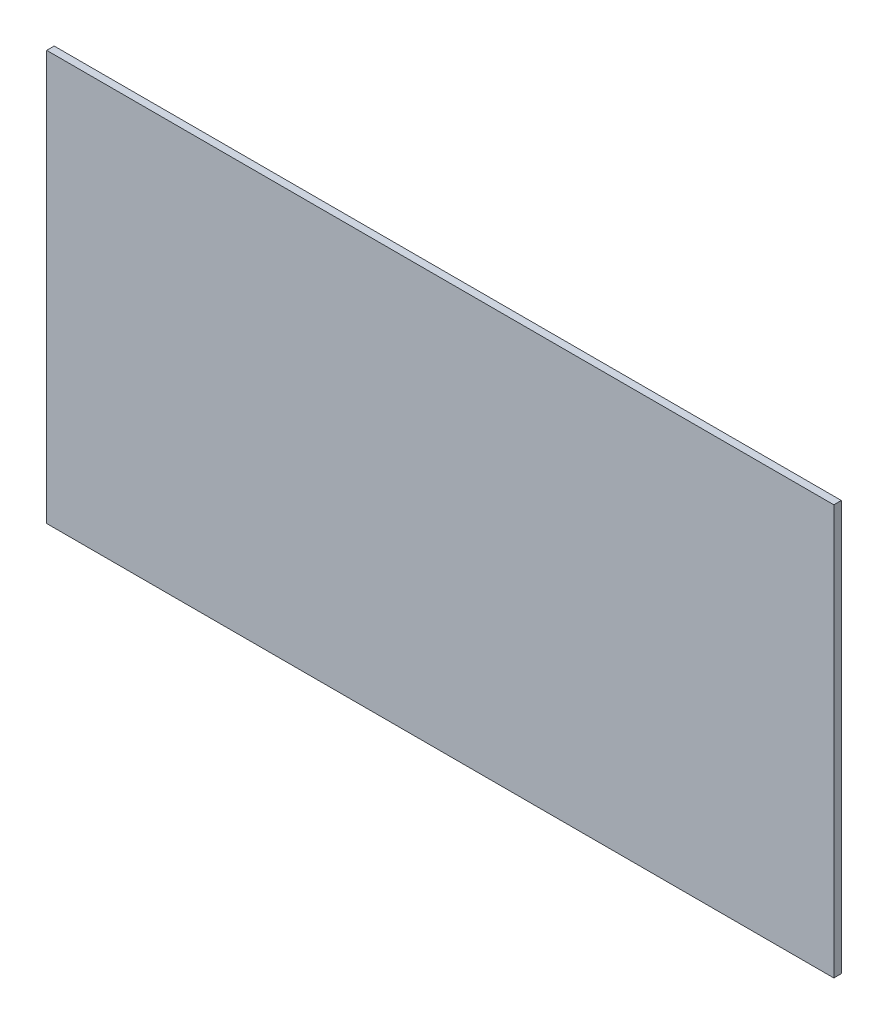
SolidWorks part; units mm, degrees
ref_plane "Ön Düzlem" through (0, 0, 0) normal (0, 0, 1) x (1, 0, 0)
ref_plane "Üst Düzlem" through (0, 0, 0) normal (0, 1, 0) x (1, 0, 0)
ref_plane "Sağ Düzlem" through (0, 0, 0) normal (1, 0, 0) x (0, 0, -1)
sketch "Çizim1" plane through (0, 0, 0) normal (0, 0, 1) x (1, 0, 0)
  line L1 (0, 0) -> (630, 0)
  line L2 (0, 0) -> (0, -328)
  line L3 (0, -328) -> (630, -328)
  line L4 (630, 0) -> (630, -328)
  dimension "D1" = 630
  dimension "D2" = 328
base flange "Taban-Flanş1" sketch "Çizim1" thickness 6 reverse thickness direction no parameters "D1"=12
sketch "Büküm-Çizgileri1" [suppressed] plane through (0, 0, 0) normal (0, 1, 0) x (1, 0, 0)
sketch "Sınırlandırma-Kutusu1" [suppressed] plane through (0, 0, 0) normal (0, 1, 0) x (1, 0, 0)
sheet metal parameters "Sac-Levha1" thickness 6 parameters "D1"=12
flat pattern "Düz-Çoğaltma1" [suppressed]
sketch "Büküm-Çizgileri2" plane through (0, 0, 0) normal (0, 1, 0) x (1, 0, 0)
sketch3d "Sınırlandırma-Kutusu2" [suppressed]
  line L0 (0, -328, 0) -> (630, -328, 0) construction
  line L1 (0, 0, 0) -> (630, 0, 0) construction
  line L2 (0, -328, 0) -> (0, 0, 0) construction
  line L3 (630, -328, 0) -> (630, 0, 0) construction
